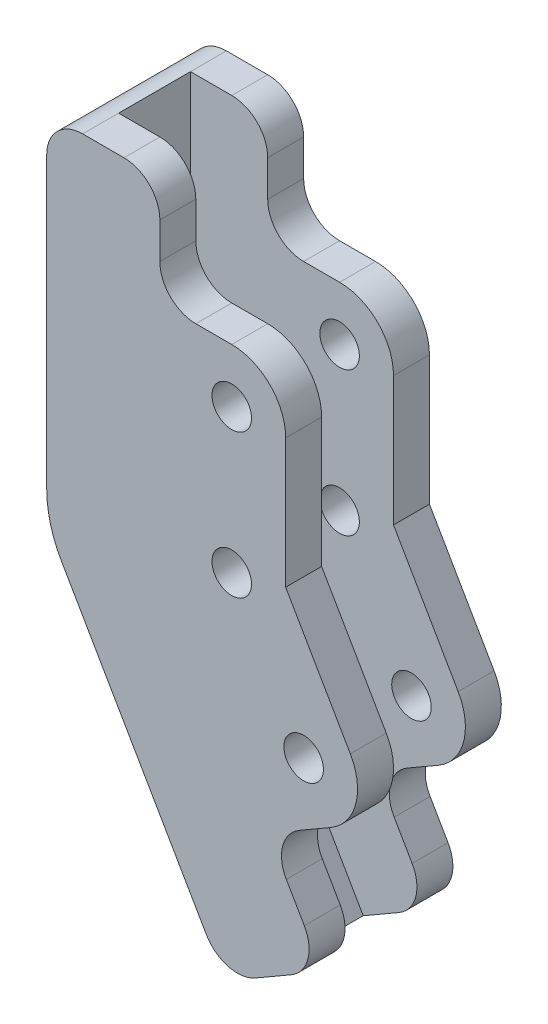
SolidWorks part; units mm, degrees
ref_plane "Front Plane" through (0, 0, 0) normal (0, 0, 1) x (1, 0, 0)
ref_plane "Top Plane" through (0, 0, 0) normal (0, 1, 0) x (1, 0, 0)
ref_plane "Right Plane" through (0, 0, 0) normal (1, 0, 0) x (0, 0, -1)
sketch "Sketch1" plane through (0, 0, 0) normal (0, 0, 1) x (1, 0, 0)
  line L0 (20.3407, 130.4503) -> (-19.6593, 119.7323)
  line L1 (0.3407, 125.0913) -> (0.3407, 145.0913)
  line L2 (0.3407, 125.0913) -> (10.3407, 107.7708)
  line L3 (21.3397, 128.0385) -> (92.3205, 5.0962) construction
  line L4 (-7.1593, 145.0913) -> (-7.1593, 125.0913)
  line L5 (7.8407, 145.0913) -> (7.8407, 125.0913)
  line L6 (-6.1544, 121.3413) -> (3.8456, 104.0208)
  line L7 (6.8359, 128.8413) -> (16.8359, 111.5208)
  line L8 (0.3407, 152.5913) -> (-9.6593, 152.5913)
  line L9 (-9.6593, 152.5913) -> (-9.6593, 167.5913)
  line L10 (14.0907, 101.2756) -> (5.4305, 96.2756)
  line L11 (5.4305, 96.2756) -> (12.9305, 83.2852)
  line L12 (-18.6603, 117.3205) -> (52.6795, -6.2436) construction
  line L13 (12.9305, 83.2852) -> (3.6287, 77.9149)
  line L14 (-9.6593, 167.5913) -> (-20.4, 167.5913)
  line L15 (-20.4, 167.5913) -> (-20.4, 122.3205)
  line L16 (-19.0067, 117.1205) -> (3.6287, 77.9149)
  arc A0 (20, 133.0385) -> (21.3397, 128.0385) centre (30, 133.0385) ccw construction
  arc A1 (-20, 122.3205) -> (-18.6603, 117.3205) centre (-10, 122.3205) ccw construction
  circle A2 centre (0.3407, 125.0913) radius 2.75
  circle A3 centre (0.3407, 145.0913) radius 2.75
  circle A4 centre (10.3407, 107.7708) radius 2.75
  circle A5 centre (0.3407, 145.0913) radius 7.5
  circle A6 centre (10.3407, 107.7708) radius 7.5
  circle A7 centre (0.3407, 125.0913) radius 7.5
  arc A8 (-20, 122.3205) -> (-18.6603, 117.3205) centre (-10, 122.3205) ccw
  arc A9 (-20.4, 122.3205) -> (-19.0067, 117.1205) centre (-10, 122.3205) ccw
  dimension "D1" = 5.5
  dimension "D4" = 5.5
  dimension "D5" = 5.5
  dimension "D6" = 15
  dimension "D7" = 10
  dimension "D2" = 20
  dimension "D3" = 20
  dimension "D8" = 15
  dimension "D9" = 10
  dimension "D10" = 15
  dimension "D11" = 10.7407
  dimension "D12" = 10.7407
  dimension "D13" = 0.4
extrude "Boss-Extrude1" add sketch "Sketch1" along normal blind 5 contours A7 L0 L7 | A7 L5 L0 | A7 L2 A6 L7 L5 | A6 A4 | A7 L6 A6 L2 | L0 A7 L2 A2 | A7 L0 A2 L2 | L0 A7 L1 A2 | L1 A7 L0 A2 | A7 L7 L5 A5 L1 | A7 L1 A5 L4 | A5 A3 | L15 A9 L16 L13 L11 L10 A6 L6 A7 L4 A5 L8 L9 L14 region at (7.7639, 126.5744, 0) region at (4.8879, 135.1367, 0) region at (9.3014, 118.6653, 0) region at (7.5109, 127.5184, 0) region at (5.06, 123.1365, 0) region at (3.4504, 129.1438, 0) region at (5.494, 139.938, 0) region at (17.3803, 109.657, 0) region at (-5.642, 151.074, 0) region at (-4.2218, 135.0913, 0) region at (-1.4789, 120.6983, 0) region at (1.3894, 114.1498, 0) region at (-3.4317, 127.986, 0)
sketch "Sketch2" plane through (0, 0, -10) normal (0, 0, -1) x (-1, 0, 0)
  line L10 (-14.0907, 101.2756) -> (-5.4305, 96.2756)
  line L11 (-5.4305, 96.2756) -> (-12.9305, 83.2852)
  line L12 (-12.9305, 83.2852) -> (-3.6287, 77.9149)
  line L13 (-3.6287, 77.9149) -> (19.0067, 117.1205)
  line L14 (20.4, 122.3205) -> (20.4, 167.5913)
  line L15 (20.4, 167.5913) -> (9.6593, 167.5913)
  line L16 (9.6593, 167.5913) -> (9.6593, 152.5913)
  line L17 (9.6593, 152.5913) -> (-0.3407, 152.5913)
  line L18 (-7.8407, 145.0913) -> (-7.8407, 127.1009)
  line L19 (-7.8407, 127.1009) -> (-16.8359, 111.5208)
  line L20 (-14.0907, 101.2756) -> (-5.4305, 96.2756)
  line L21 (-5.4305, 96.2756) -> (-12.9305, 83.2852)
  line L22 (-12.9305, 83.2852) -> (-3.6287, 77.9149)
  line L23 (-3.6287, 77.9149) -> (19.0067, 117.1205)
  line L24 (20.4, 122.3205) -> (20.4, 167.5913)
  line L25 (20.4, 167.5913) -> (9.6593, 167.5913)
  line L26 (9.6593, 167.5913) -> (9.6593, 152.5913)
  line L27 (9.6593, 152.5913) -> (-0.3407, 152.5913)
  line L28 (-7.8407, 145.0913) -> (-7.8407, 127.1009)
  line L29 (-7.8407, 127.1009) -> (-16.8359, 111.5208)
  circle A0 centre (-10.3407, 107.7708) radius 2.75 construction
  circle A1 centre (-0.3407, 125.0913) radius 2.75 construction
  circle A2 centre (-0.3407, 145.0913) radius 2.75 construction
  arc A3 (19.0067, 117.1205) -> (20.4, 122.3205) centre (10, 122.3205) ccw
  arc A4 (-0.3407, 152.5913) -> (-7.8407, 145.0913) centre (-0.3407, 145.0913) ccw
  arc A5 (-16.8359, 111.5208) -> (-14.0907, 101.2756) centre (-10.3407, 107.7708) ccw
  arc A6 (19.0067, 117.1205) -> (20.4, 122.3205) centre (10, 122.3205) ccw
  arc A7 (-0.3407, 152.5913) -> (-7.8407, 145.0913) centre (-0.3407, 145.0913) ccw
  arc A8 (-16.8359, 111.5208) -> (-14.0907, 101.2756) centre (-10.3407, 107.7708) ccw
  circle A9 centre (-10.3407, 107.7708) radius 2.75
  circle A10 centre (-0.3407, 125.0913) radius 2.75
  circle A11 centre (-0.3407, 145.0913) radius 2.75
  dimension "D1" = 0
extrude "Boss-Extrude2" add sketch "Sketch2" along normal blind 5 separate body
sketch "Sketch3" plane through (0, 0, 5) normal (0, 0, 1) x (1, 0, 0)
  line L5 (-0.7014, 75.4149) -> (3.6287, 77.9149)
  line L6 (-20.4, 167.5913) -> (-20.4, 122.3205) construction
  line L7 (-23.3368, 114.6205) -> (-0.7014, 75.4149)
  line L8 (-25.4, 167.5913) -> (-25.4, 122.3205)
  line L9 (-23.3368, 114.6205) -> (-0.7014, 75.4149)
  line L10 (-25.4, 167.5913) -> (-25.4, 122.3205)
  line L11 (-19.0067, 117.1205) -> (3.6287, 77.9149) construction
  line L12 (-20.4, 167.5913) -> (-20.4, 122.3205)
  line L13 (-19.0067, 117.1205) -> (3.6287, 77.9149)
  line L14 (-25.4, 167.5913) -> (-20.4, 167.5913)
  arc A1 (-20.4, 122.3205) -> (-19.0067, 117.1205) centre (-10, 122.3205) ccw construction
  arc A2 (-25.4, 122.3205) -> (-23.3368, 114.6205) centre (-10, 122.3205) ccw
  arc A3 (-25.4, 122.3205) -> (-23.3368, 114.6205) centre (-10, 122.3205) ccw
  arc A4 (-20.4, 122.3205) -> (-19.0067, 117.1205) centre (-10, 122.3205) ccw
  dimension "D1" = 5
extrude "Boss-Extrude3" add sketch "Sketch3" against normal up to surface (20 mm away) up to face at (-2.4093, 125.0913, -15)
fillet "Fillet1" radius 5 10 edges at (-25.4, 167.5913, -5) (-0.7014, 75.4149, -5) (12.9305, 83.2852, -12.5) (12.9305, 83.2852, 2.5) (5.4305, 96.2756, 2.5) (5.4305, 96.2756, -12.5) (-9.6593, 167.5913, 2.5) (-9.6593, 152.5913, 2.5) (-9.6593, 152.5913, -12.5) (-9.6593, 167.5913, -12.5)
